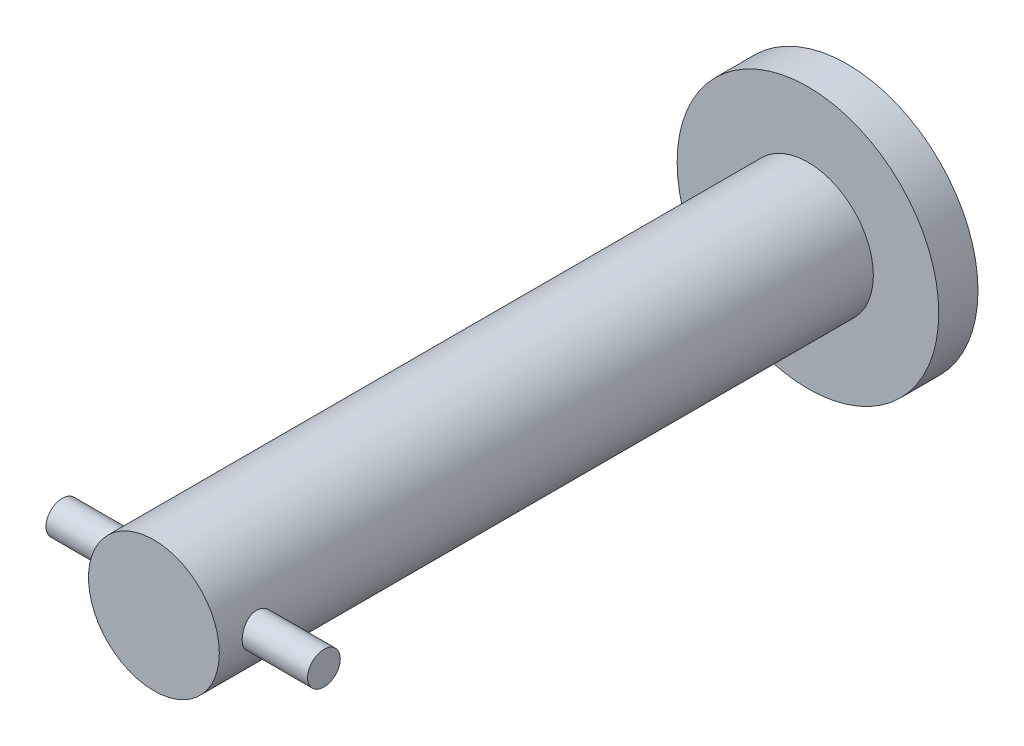
SolidWorks part; units mm, degrees
material "Cast Stainless Steel"
ref_plane "Front Plane" through (0, 0, 0) normal (0, 0, 1) x (1, 0, 0)
ref_plane "Top Plane" through (0, 0, 0) normal (0, 1, 0) x (1, 0, 0)
ref_plane "Right Plane" through (0, 0, 0) normal (1, 0, 0) x (0, 0, -1)
sketch "Sketch1" plane through (0, 0, 0) normal (0, 0, 1) x (1, 0, 0)
  circle A0 centre (0, 0) radius 5
  circle A1 centre (0, 0) radius 10
  dimension "D1" = 10
  dimension "D2" = 20
extrude "Boss-Extrude1" add sketch "Sketch1" along normal blind 5
extrude "Boss-Extrude2" add sketch "Sketch1<2>" along normal blind 55 contours A0 region at (0, 0, 0)
sketch "Sketch1<2>" plane through (0, 0, 0) normal (0, 0, 1) x (1, 0, 0) same geometry as "Sketch1"
chamfer "Chamfer1" distance 3 distance2 2 1 edges at (10, 0, 0) first distance on face at (10, 0, 0)
sketch "Sketch2" plane through (0, 0, 0) normal (1, 0, 0) x (0, 0, -1)
  line L0 (8.6955, 0) -> (-62.9768, 0) construction
  line L1 (-5, 10) -> (-5, -10) construction
  circle A0 centre (-52, 0) radius 1.25
  dimension "D1" = 2.5
  dimension "D2" = 47
extrude "Boss-Extrude3" add sketch "Sketch2" along normal blind 10 and the other way blind 10
ref_plane "Plane1" through (0, 0, 27) normal (0, 0, 1) x (1, 0, 0)
sketch "Sketch4" plane through (0, 0, 27) normal (0, 0, 1) x (1, 0, 0)
  circle A0 centre (0, 0) radius 6 construction
  dimension "D1" = 12
sketch "Sketch6" plane through (0, 0, 0) normal (0, 0, 1) x (1, 0, 0)
  circle A0 centre (0, 0) radius 500 construction
  dimension "D1" = 1000
